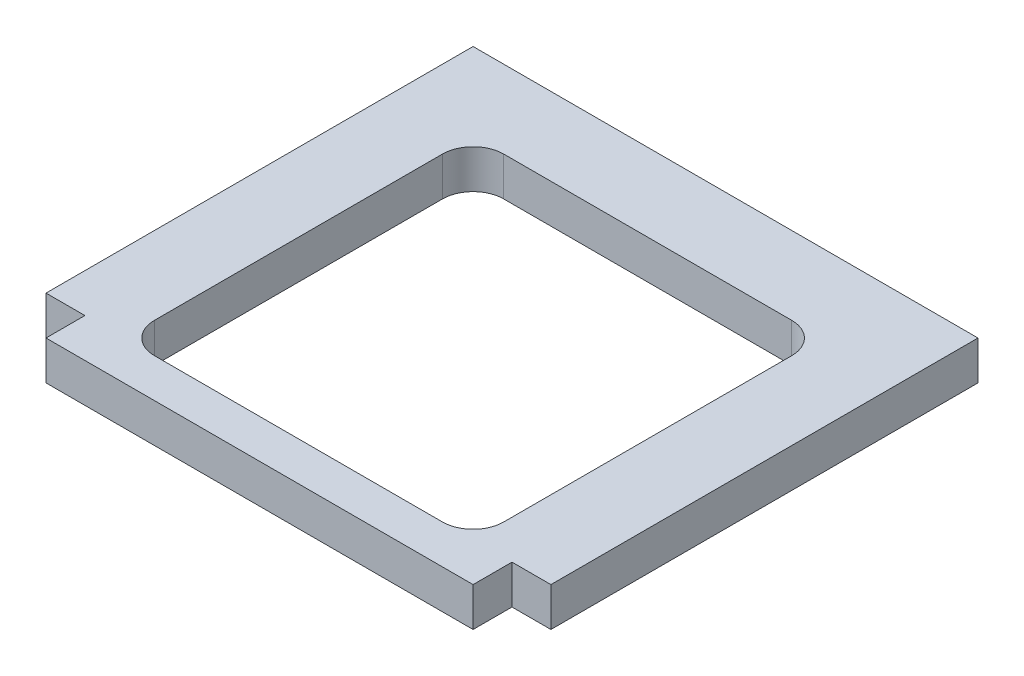
SolidWorks part; units mm, degrees
ref_plane "Front Plane" through (0, 0, 0) normal (0, 0, 1) x (1, 0, 0)
ref_plane "Top Plane" through (0, 0, 0) normal (0, 1, 0) x (1, 0, 0)
ref_plane "Right Plane" through (0, 0, 0) normal (1, 0, 0) x (0, 0, -1)
sketch "Sketch1" plane through (0, 0, 0) normal (0, 1, 0) x (1, 0, 0)
  line L0 (-41.2, -28.5) -> (-41.2, 41.2)
  line L1 (-23.5, -28.5) -> (23.5, -28.5)
  line L2 (-28.5, -23.5) -> (-28.5, 23.5)
  line L3 (-23.5, 28.5) -> (23.5, 28.5)
  line L4 (28.5, -23.5) -> (28.5, 23.5)
  line L5 (-28.5, -28.5) -> (28.5, 28.5) construction
  line L6 (-28.5, 28.5) -> (28.5, -28.5) construction
  line L7 (-41.2, 41.2) -> (41.2, 41.2)
  line L8 (41.2, -28.5) -> (41.2, 41.2)
  line L9 (28.5, -28.5) -> (28.5, 28.5) construction
  line L10 (-34.85, -34.85) -> (34.85, -34.85)
  line L11 (-41.2, -41.2) -> (-41.2, 41.2) construction
  line L12 (-41.2, -41.2) -> (41.2, -41.2) construction
  line L13 (41.2, -41.2) -> (41.2, 41.2) construction
  line L14 (-28.5, 28.5) -> (28.5, 28.5) construction
  line L15 (-28.5, -28.5) -> (28.5, -28.5) construction
  line L16 (-28.5, -28.5) -> (-28.5, 28.5) construction
  line L17 (-41.2, -28.5) -> (-34.85, -28.5)
  line L18 (-34.85, -34.85) -> (-34.85, -28.5)
  line L21 (41.2, -28.5) -> (34.85, -28.5)
  line L22 (34.85, -34.85) -> (34.85, -28.5)
  arc A0 (28.5, 23.5) -> (23.5, 28.5) centre (23.5, 23.5) ccw
  arc A1 (28.5, -23.5) -> (23.5, -28.5) centre (23.5, -23.5) cw
  arc A2 (-23.5, -28.5) -> (-28.5, -23.5) centre (-23.5, -23.5) cw
  arc A3 (-28.5, 23.5) -> (-23.5, 28.5) centre (-23.5, 23.5) cw
  point P0 (0, 0)
  dimension "D7" = 5
  dimension "D1" = 57
  dimension "D2" = 57
  dimension "D4" = 6.35
  dimension "D5" = 6.35
  dimension "D6" = 6.35
  dimension "D3" = 12.7
extrude "Boss-Extrude1" add sketch "Sketch1" along normal blind 6.35
